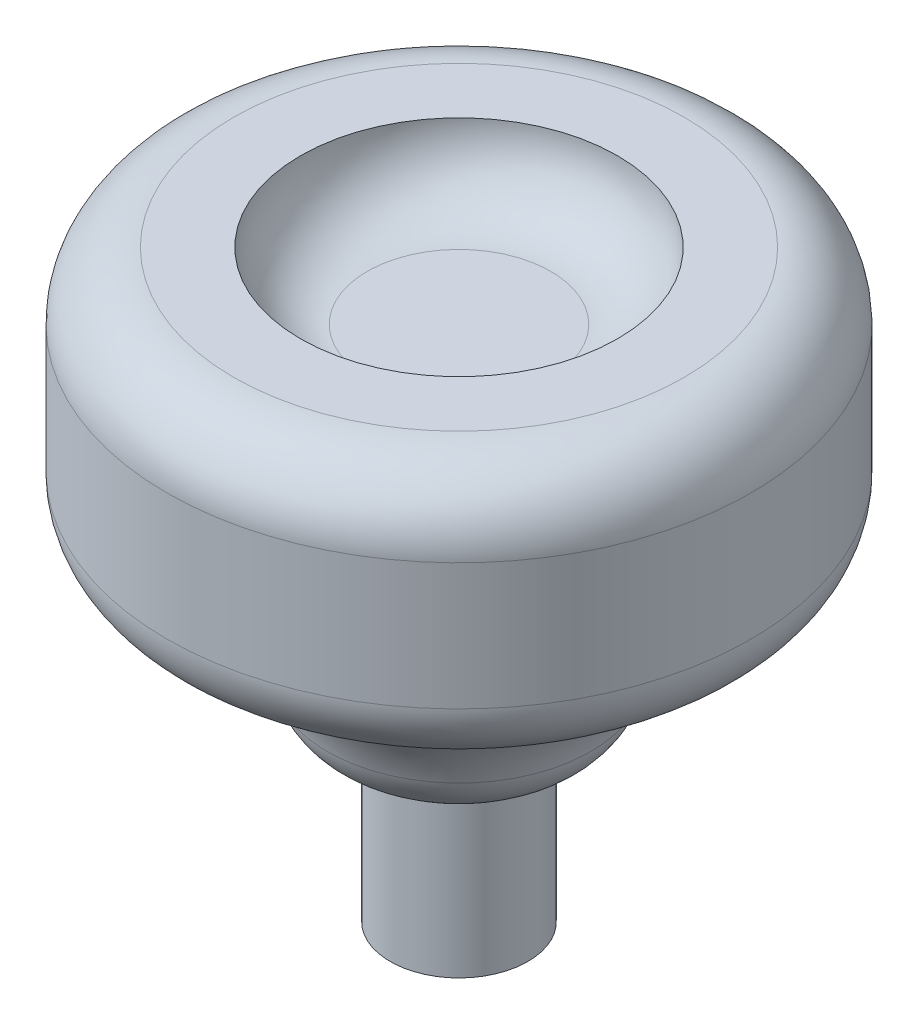
SolidWorks part; units mm, degrees
ref_plane "Front" through (0, 0, 0) normal (0, 0, 1) x (1, 0, 0)
ref_plane "Top" through (0, 0, 0) normal (0, 1, 0) x (-1, 0, 0)
ref_plane "Right" through (0, 0, 0) normal (1, 0, 0) x (0, 0, -1)
sketch "Sketch1" plane through (0, 0, 0) normal (0, 0, 1) x (1, 0, 0)
  line L0 (0, 0) -> (0, 36.2882) construction
  line L1 (0, 0) -> (0, 22.225)
  line L2 (0, 22.225) -> (11.1125, 22.225)
  line L3 (11.1125, 12.7) -> (11.1125, 22.225)
  line L4 (4.7625, 6.35) -> (3.175, 6.35)
  line L5 (3.175, 6.35) -> (3.175, 0)
  line L6 (3.175, 0) -> (0, 0)
  arc A0 (11.1125, 22.225) -> (11.1125, 12.7) centre (11.1125, 17.4625) cw
  arc A1 (11.1125, 12.7) -> (4.7625, 6.35) centre (11.1125, 6.35) ccw
  dimension "D5" = 6.35
  dimension "D6" = 4.7625
  dimension "D1" = 6.35
  dimension "D2" = 4.7625
  dimension "D3" = 6.35
  dimension "D4" = 15.875
revolve "Base-Revolve" add sketch "Sketch1" angle 360 about L0 region at (4.5215, 13.9357, 0)
fillet "Fillet1" radius 2.54 3 edges at (0, 12.7, -11.1125) (0, 6.35, -4.7625) (0, 22.225, -11.1125)
sketch "Sketch2" plane through (0, 22.225, 0) normal (0, 1, 0) x (1, 0, 0)
  circle A0 centre (0, 0) radius 6.0325
  circle A1 centre (0, 0) radius 8.5725 construction
  dimension "D1" = 2.54
extrude "Cut-Extrude1" cut sketch "Sketch2" against normal blind 2.54
fillet "Fillet2" radius 2.54 1 edges at (0, 19.685, 6.0325)
sketch "Sketch4" plane through (0, 0, 0) normal (0, -1, 0) x (1, 0, 0)
  circle A0 centre (0, 0) radius 2.62
  dimension "D1" = 5.24
extrude "Cut-Extrude2" cut sketch "Sketch4" against normal blind 6.35 flip side to cut
